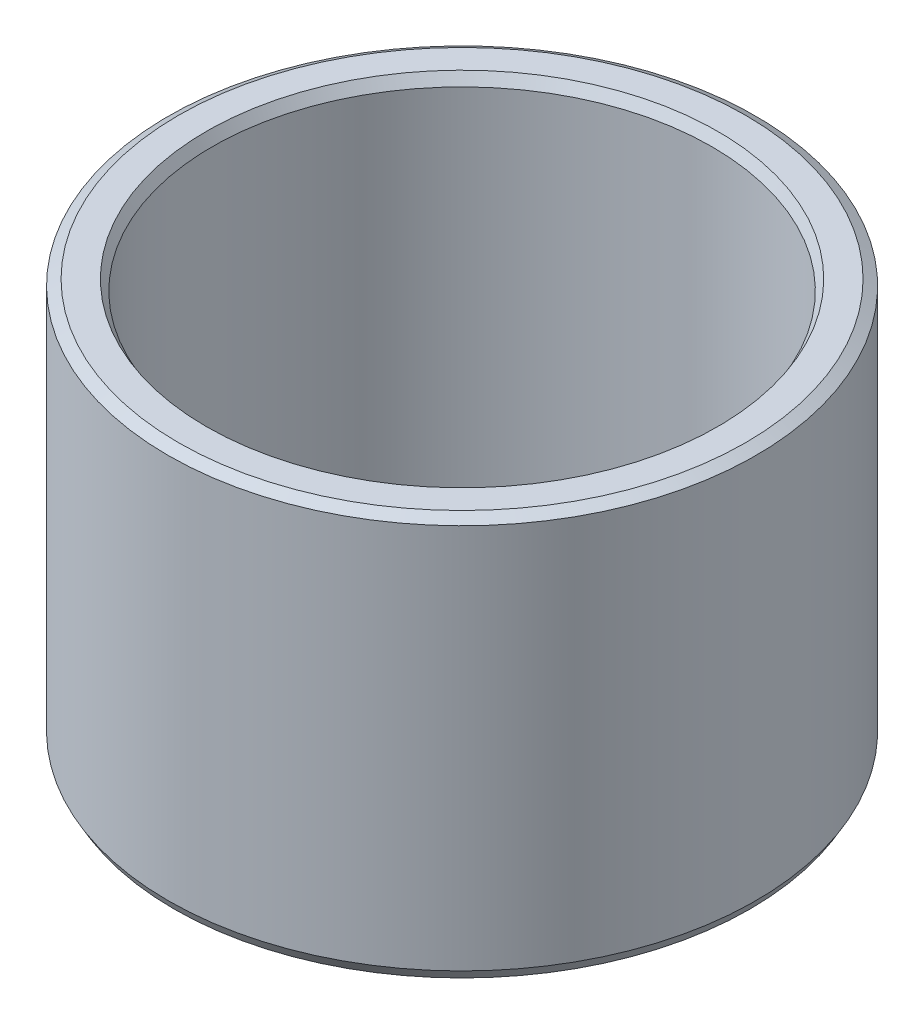
SolidWorks part; units mm, degrees
ref_plane "Front Plane" through (0, 0, 0) normal (0, 0, 1) x (1, 0, 0)
ref_plane "Top Plane" through (0, 0, 0) normal (0, 1, 0) x (1, 0, 0)
ref_plane "Right Plane" through (0, 0, 0) normal (1, 0, 0) x (0, 0, -1)
sketch "Sketch1" plane through (0, 0, 0) normal (0, 1, 0) x (1, 0, 0)
  circle A0 centre (0, 0) radius 32.5
  dimension "SLEEVE_OD" = 65
extrude "Boss-Extrude1" add sketch "Sketch1" along normal blind 44.4366
sketch "Sketch2" plane through (0, 0, 0) normal (0, 1, 0) x (1, 0, 0)
  circle A0 centre (0, 0) radius 27.6288
  dimension "BORE_D" = 55.2577
extrude "Cut-Extrude1" cut sketch "Sketch2" along normal through all
chamfer "Chamfer1" distance 0.6569 angle 60 4 edges at (0, 44.4366, 27.6288) (0, 0, 27.6288) (0, 0, 32.5) (0, 44.4366, 32.5) first distance on face at (0, 44.4366, 27.6288) first distance on face at (0, 0, 27.6288) first distance on face at (0, 44.4366, 32.5)
